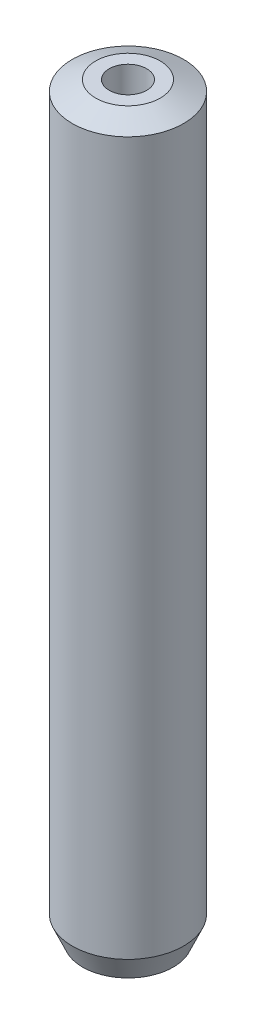
SolidWorks part; units mm, degrees
ref_plane "Front Plane" through (0, 0, 0) normal (0, 0, 1) x (1, 0, 0)
ref_plane "Top Plane" through (0, 0, 0) normal (0, 1, 0) x (1, 0, 0)
ref_plane "Right Plane" through (0, 0, 0) normal (1, 0, 0) x (0, 0, -1)
sketch "Sketch1" plane through (0, 0, 0) normal (0, 1, 0) x (1, 0, 0)
  circle A0 centre (0, 0) radius 15
  dimension "SHAFT_OD" = 30
extrude "Boss-Extrude1" add sketch "Sketch1" along normal blind 201.1042
sketch "Sketch2" plane through (0, 0, 0) normal (0, 1, 0) x (1, 0, 0)
  circle A0 centre (0, 0) radius 5.056
  dimension "BORE_D" = 10.1119
extrude "Cut-Extrude1" cut sketch "Sketch2" along normal through all
chamfer "Chamfer1" distance 2.7785 angle 66.246 2 edges at (0, 201.1042, 15) (0, 0, 15) first distance on face at (0, 201.1042, 15) first distance on face at (0, 0, 5.056)
